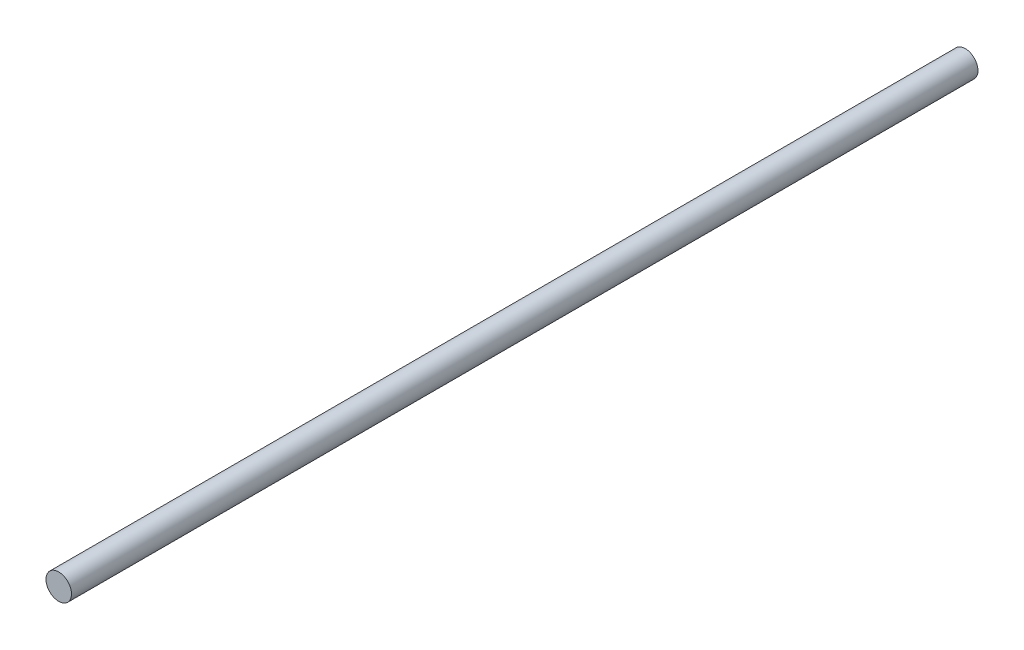
SolidWorks part; units mm, degrees
ref_plane "Front Plane" through (0, 0, 0) normal (0, 0, 1) x (1, 0, 0)
ref_plane "Top Plane" through (0, 0, 0) normal (0, 1, 0) x (1, 0, 0)
ref_plane "Right Plane" through (0, 0, 0) normal (1, 0, 0) x (0, 0, -1)
sketch "Sketch1" plane through (0, 0, 0) normal (0, 0, 1) x (1, 0, 0)
  circle A0 centre (0, 0) radius 1.45
  dimension "D1" = 2.9
extrude "Boss-Extrude1" add sketch "Sketch1" along normal blind 103
